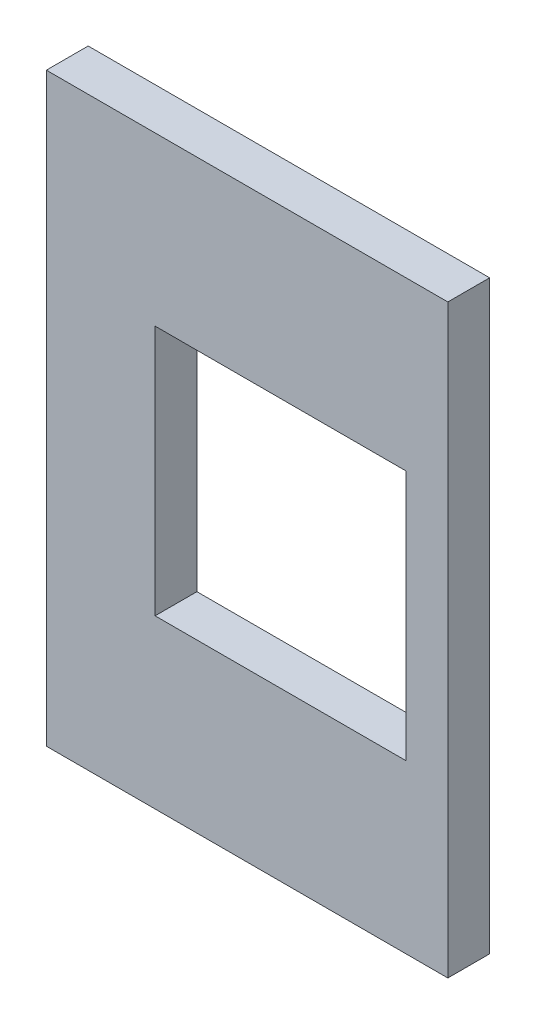
SolidWorks part; units mm, degrees
ref_plane "Front Plane" through (0, 0, 0) normal (0, 0, 1) x (1, 0, 0)
ref_plane "Top Plane" through (0, 0, 0) normal (0, 1, 0) x (1, 0, 0)
ref_plane "Right Plane" through (0, 0, 0) normal (1, 0, 0) x (0, 0, -1)
sketch "Sketch1" plane through (0, 0, 0) normal (0, 0, 1) x (1, 0, 0)
  line L0 (0, 22.225) -> (0, -22.225) construction
  line L1 (-12.7, -22.225) -> (12.7, -22.225)
  line L2 (-12.7, -22.225) -> (-12.7, 22.225)
  line L3 (-12.7, 22.225) -> (12.7, 22.225)
  line L4 (12.7, -22.225) -> (12.7, 22.225)
  line L5 (-12.7, -22.225) -> (12.7, 22.225) construction
  line L6 (-12.7, 22.225) -> (12.7, -22.225) construction
  line L7 (-9.525, 9.525) -> (9.525, 9.525)
  line L8 (-9.525, 9.525) -> (-9.525, -9.525)
  line L9 (-9.525, -9.525) -> (9.525, -9.525)
  line L10 (9.525, 9.525) -> (9.525, -9.525)
  point P0 (0, 0)
  dimension "D1" = 25.4
  dimension "D2" = 19.05
  dimension "D3" = 19.05
  dimension "D4" = 12.7
  dimension "D5" = 12.7
extrude "Boss-Extrude1" add sketch "Sketch1" along normal blind 3.175
ref_plane "Plane1" through (6.35, 0, 0) normal (1, 0, 0) x (0, 0, -1)
sketch "Sketch2" plane through (6.35, 0, 0) normal (1, 0, 0) x (0, 0, -1)
  line L0 (0, -9.525) -> (5.715, -9.525)
  line L1 (0, -22.225) -> (0, 22.225) construction
  line L2 (0, -22.225) -> (5.715, -22.225)
  line L3 (0, -9.525) -> (0, -22.225)
  circle A0 centre (5.715, -15.875) radius 3.175
  arc A1 (5.715, -22.225) -> (5.715, -9.525) centre (5.715, -15.875) ccw
  dimension "D1" = 3.175
  dimension "D2" = 6.35
  dimension "D3" = 2.54
extrude "Boss-Extrude2" [suppressed] add sketch "Sketch2" against normal blind 3.175
mirror "Mirror1" [suppressed] about plane through (0, 0, 0) normal (1, 0, 0)
sketch "Sketch3" plane through (0, 0, 0) normal (0, 0, -1) x (-1, 0, 0)
  line L4 (-12.7, -22.225) -> (12.7, -22.225)
  line L5 (-12.7, 22.225) -> (-12.7, -22.225)
  line L6 (-12.7, 22.225) -> (-12.7, -22.225)
  line L7 (12.7, -22.225) -> (12.7, 22.225)
  line L8 (-12.7, -22.225) -> (12.7, -22.225)
  line L12 (12.7, -22.225) -> (12.7, 22.225)
  line L13 (12.7, 22.225) -> (-12.7, 22.225)
  line L14 (12.7, 22.225) -> (-12.7, 22.225)
  dimension "D1" = 0
extrude "Cut-Extrude1" [suppressed] cut sketch "Sketch3" against normal through all
sketch "Sketch4" plane through (-12.7, 0, 0) normal (-1, 0, 0) x (0, 0, 1)
  line L4 (0, 22.225) -> (0, -22.225)
  line L5 (0, -22.225) -> (3.175, -22.225)
  line L6 (3.175, -22.225) -> (3.175, 22.225)
  line L7 (3.175, 22.225) -> (0, 22.225)
  line L8 (0, 22.225) -> (0, -22.225)
  line L9 (0, -22.225) -> (3.175, -22.225)
  line L10 (3.175, -22.225) -> (3.175, 22.225)
  line L11 (3.175, 22.225) -> (0, 22.225)
  dimension "D1" = 0
extrude "Boss-Extrude3" add sketch "Sketch4" along normal blind 5.08
